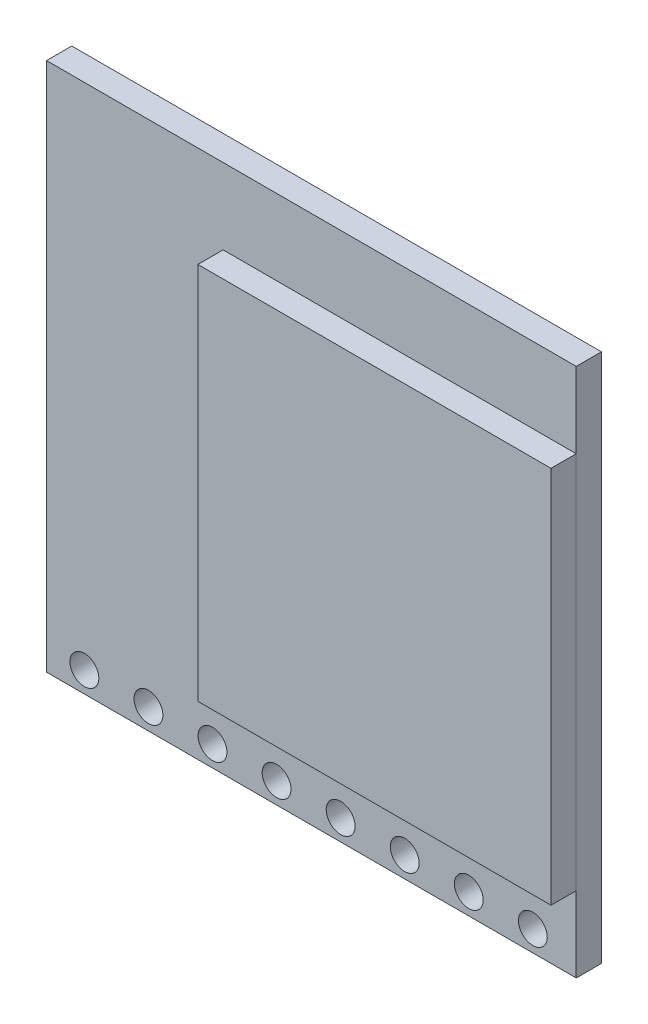
SolidWorks part; units mm, degrees
note: '?' marks a value the reader was unsure of.
ref_plane "Спереди" through (0, 0, 0) normal (0, 0, 1) x (1, 0, 0)
ref_plane "Сверху" through (0, 0, 0) normal (0, 1, 0) x (1, 0, 0)
ref_plane "Справа" through (0, 0, 0) normal (1, 0, 0) x (0, 0, -1)
sketch "Sketch1" plane through (0, 0, 0) normal (0, 0, 1) x (1, 0, 0)
  line L1 (0, 0) -> (21, 0)
  line L2 (0, 0) -> (0, 21)
  line L3 (0, 21) -> (21, 21)
  line L4 (21, 0) -> (21, 21)
  dimension "D1" = 21
  dimension "D2" = 21
extrude "Boss-Extrude1" add sketch "Sketch1" along normal blind 1
sketch "Sketch2" plane through (0, 0, 1) normal (0, 0, 1) x (1, 0, 0)
  line L0 (21, 0) -> (21, 21) construction
  line L1 (21, 18) -> (7, 18)
  line L2 (21, 18) -> (21, 3)
  line L3 (21, 3) -> (7, 3)
  line L4 (7, 18) -> (7, 3)
  dimension "D1" = 14
  dimension "D2" = 3
  dimension "D3" = 3
extrude "Boss-Extrude2" add sketch "Sketch2" along normal blind 1 separate body
sketch "Sketch3" plane through (0, 0, 1) normal (0, 0, 1) x (1, 0, 0)
  line L0 (0, 21) -> (0, 0) construction
  circle A0 centre (1.5, 0.8266) radius 0.572
  dimension "D1" = 1.5
extrude "Cut-Extrude1" cut sketch "Sketch3" against normal blind 1
pattern_linear "LPattern1" count 8 spacing 2.54 along (1, 0, 0) of "Cut-Extrude1"
ref_axis "Axis1" through (1.5, 0.8266, 0) along (0, 0, 1)?
